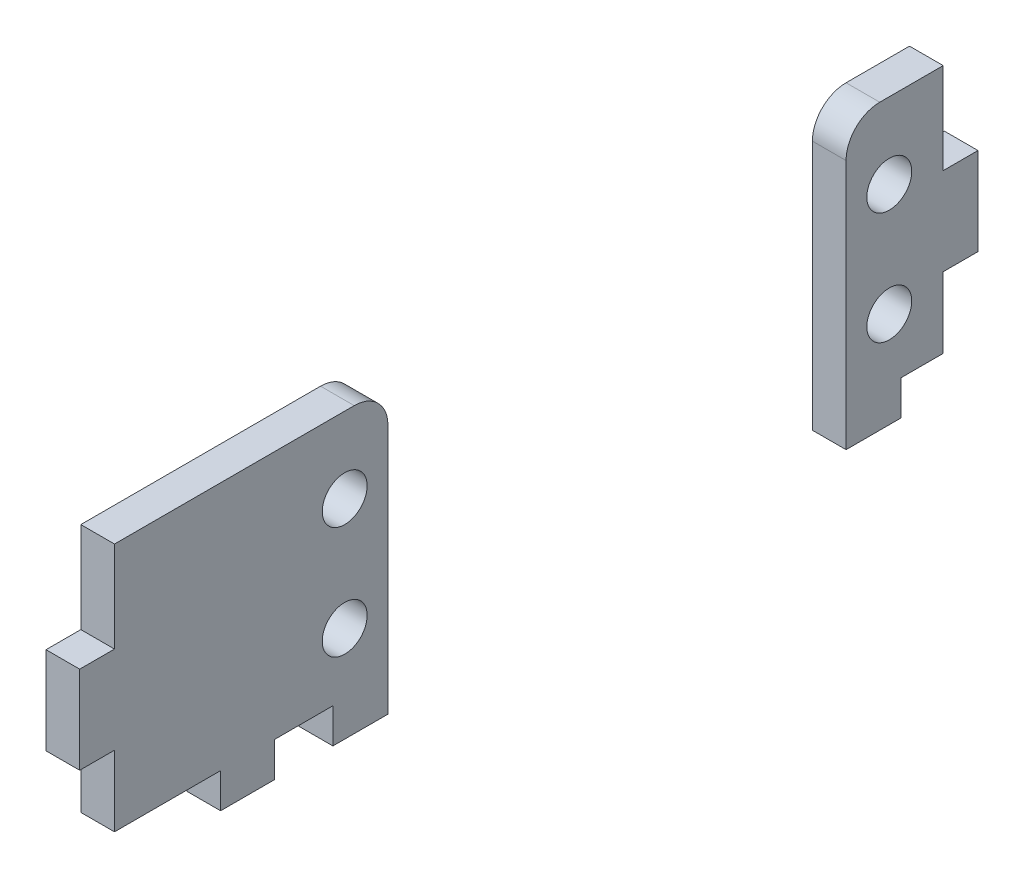
SolidWorks part; units mm, degrees
ref_plane "Front Plane" through (0, 0, 0) normal (0, 0, 1) x (1, 0, 0)
ref_plane "Top Plane" through (0, 0, 0) normal (0, 1, 0) x (1, 0, 0)
ref_plane "Right Plane" through (0, 0, 0) normal (1, 0, 0) x (0, 0, -1)
sketch "Sketch1" plane through (0, 0, 0) normal (1, 0, 0) x (0, 0, -1)
  line L0 (27.45, 0) -> (27.45, -25.3)
  line L1 (0, 0) -> (80, 0) construction
  line L2 (0, 0) -> (0, -25.3)
  line L3 (0, -25.3) -> (80, -25.3) construction
  line L4 (80, 0) -> (80, -25.3)
  line L5 (68.25, 0) -> (68.25, -25.3)
  line L6 (27.45, 0) -> (27.45, -22.3) construction
  line L7 (68.25, 0) -> (68.25, -22.3) construction
  line L8 (0, 0) -> (27.45, 0)
  line L9 (68.25, 0) -> (80, 0)
  line L10 (80, -25.3) -> (68.25, -25.3)
  line L11 (27.45, -25.3) -> (0, -25.3)
  circle A0 centre (23.6, -6.75) radius 3.8 construction
  circle A1 centre (23.6, -6.75) radius 2 construction
  circle A2 centre (72.1, -6.75) radius 3.8 construction
  circle A3 centre (72.1, -6.75) radius 2 construction
  circle A4 centre (72.1, -16.75) radius 2 construction
  circle A5 centre (72.1, -16.75) radius 3.8 construction
  circle A6 centre (23.6, -16.75) radius 3.8 construction
  circle A7 centre (23.6, -16.75) radius 2 construction
  circle A8 centre (23.6, -6.75) radius 3.8 construction
  circle A9 centre (23.6, -6.75) radius 2
  circle A10 centre (72.1, -6.75) radius 3.8 construction
  circle A11 centre (72.1, -6.75) radius 2
  circle A12 centre (72.1, -16.75) radius 2
  circle A13 centre (72.1, -16.75) radius 3.8 construction
  circle A14 centre (23.6, -16.75) radius 3.8 construction
  circle A15 centre (23.6, -16.75) radius 2
sketch "Sketch2" plane through (0, 0, 0) normal (0, 0, 1) x (1, 0, 0)
  line L0 (12, -40.925) -> (15, -40.925) construction
  line L1 (-3, 0) -> (0, 0)
  line L2 (-3, 0) -> (-3, -25.3)
  line L3 (-3, -25.3) -> (0, -25.3)
  line L4 (0, 0) -> (0, -25.3)
extrude "Boss-Extrude1" add sketch "Sketch1" against normal up to vertex (3 mm away) up to point (-3, 0, 0)
sketch "Sketch3" plane through (0, 0, 0) normal (1, 0, 0) x (0, 0, -1)
  line L4 (17.45, -22.3) -> (17.45, -25.3)
  line L5 (17.45, -25.3) -> (22.45, -25.3)
  line L6 (22.45, -25.3) -> (22.45, -22.3)
  line L7 (22.45, -22.3) -> (17.45, -22.3)
  line L8 (17.45, -22.3) -> (17.45, -25.3) construction
  line L9 (17.45, -25.3) -> (22.45, -25.3) construction
  line L10 (22.45, -25.3) -> (22.45, -22.3) construction
  line L11 (22.45, -22.3) -> (17.45, -22.3) construction
  line L12 (77, 0) -> (77, -8)
  line L13 (80, 0) -> (77, 0)
  line L14 (80, -8) -> (80, 0)
  line L15 (77, -8) -> (80, -8)
  line L16 (77, 0) -> (77, -8) construction
  line L17 (80, 0) -> (77, 0) construction
  line L18 (80, -8) -> (80, 0) construction
  line L19 (77, -8) -> (80, -8) construction
  line L20 (3, -8) -> (3, 0)
  line L21 (3, 0) -> (0, 0)
  line L22 (0, 0) -> (0, -8)
  line L23 (0, -8) -> (3, -8)
  line L24 (3, -8) -> (3, 0) construction
  line L25 (3, 0) -> (0, 0) construction
  line L26 (0, 0) -> (0, -8) construction
  line L27 (0, -8) -> (3, -8) construction
  line L30 (77, -16) -> (77, -22.3)
  line L31 (80, -16) -> (77, -16)
  line L32 (80, -25.3) -> (80, -16)
  line L33 (73.25, -25.3) -> (80, -25.3)
  line L34 (73.25, -22.3) -> (73.25, -25.3)
  line L35 (77, -22.3) -> (73.25, -22.3)
  line L36 (77, -16) -> (77, -22.3) construction
  line L37 (80, -16) -> (77, -16) construction
  line L38 (80, -25.3) -> (80, -16) construction
  line L39 (73.25, -25.3) -> (80, -25.3) construction
  line L40 (73.25, -22.3) -> (73.25, -25.3) construction
  line L41 (77, -22.3) -> (73.25, -22.3) construction
  line L42 (12.45, -22.3) -> (3, -22.3)
  line L43 (12.45, -25.3) -> (12.45, -22.3)
  line L44 (0, -25.3) -> (12.45, -25.3)
  line L45 (0, -16) -> (0, -25.3)
  line L46 (3, -16) -> (0, -16)
  line L47 (3, -22.3) -> (3, -16)
  line L48 (12.45, -22.3) -> (3, -22.3) construction
  line L49 (12.45, -25.3) -> (12.45, -22.3) construction
  line L50 (0, -25.3) -> (12.45, -25.3) construction
  line L51 (0, -16) -> (0, -25.3) construction
  line L52 (3, -16) -> (0, -16) construction
  line L53 (3, -22.3) -> (3, -16) construction
  line L72 (17.35, -22.2) -> (17.35, -25.4)
  line L73 (17.35, -25.4) -> (22.55, -25.4)
  line L74 (22.55, -25.4) -> (22.55, -22.2)
  line L75 (22.55, -22.2) -> (17.35, -22.2)
  line L76 (76.9, 0.1) -> (76.9, -8.1)
  line L77 (76.9, -8.1) -> (80.1, -8.1)
  line L78 (80.1, -8.1) -> (80.1, 0.1)
  line L79 (80.1, 0.1) -> (76.9, 0.1)
  line L80 (3.1, -8.1) -> (3.1, 0.1)
  line L81 (3.1, 0.1) -> (-0.1, 0.1)
  line L82 (-0.1, 0.1) -> (-0.1, -8.1)
  line L83 (-0.1, -8.1) -> (3.1, -8.1)
  line L84 (76.9, -15.9) -> (76.9, -22.2)
  line L85 (76.9, -22.2) -> (73.15, -22.2)
  line L86 (73.15, -22.2) -> (73.15, -25.4)
  line L87 (73.15, -25.4) -> (80.1, -25.4)
  line L88 (80.1, -25.4) -> (80.1, -15.9)
  line L89 (80.1, -15.9) -> (76.9, -15.9)
  line L90 (12.55, -22.2) -> (3.1, -22.2)
  line L91 (3.1, -22.2) -> (3.1, -15.9)
  line L92 (3.1, -15.9) -> (-0.1, -15.9)
  line L93 (-0.1, -15.9) -> (-0.1, -25.4)
  line L94 (-0.1, -25.4) -> (12.55, -25.4)
  line L95 (12.55, -25.4) -> (12.55, -22.2)
  dimension "D1" = 0
  dimension "D2" = 0
  dimension "D3" = 0
  dimension "D4" = 0
  dimension "D5" = 0
  dimension "D6" = 0.1
extrude "Cut-Extrude1" cut sketch "Sketch3" against normal through all
fillet "Fillet1" radius 3 1 edges at (-1.5, 0, -27.45)
fillet "Fillet2" radius 3 1 edges at (-1.5, 0, -68.25)
